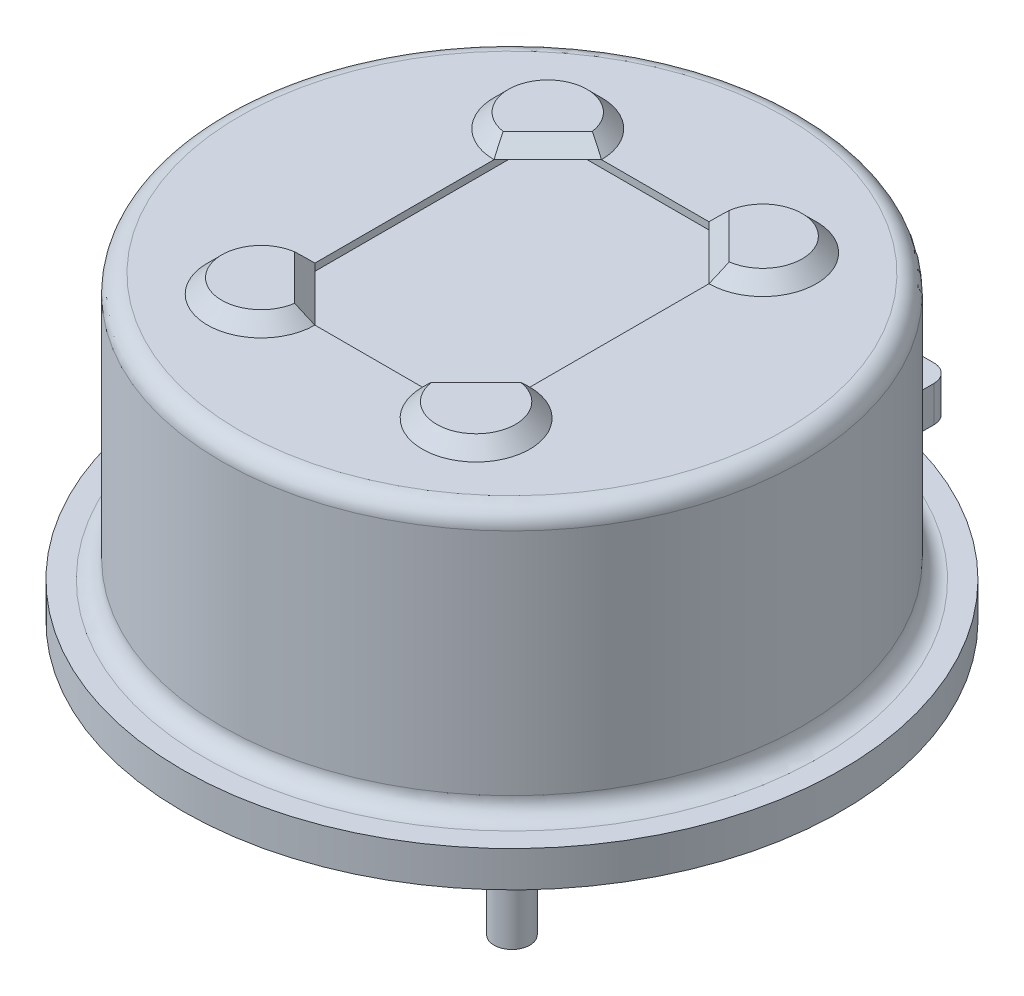
SolidWorks part; units mm, degrees
ref_plane "Front Plane" through (0, 0, 0) normal (0, 0, 1) x (1, 0, 0)
ref_plane "Top Plane" through (0, 0, 0) normal (0, 1, 0) x (1, 0, 0)
ref_plane "Right Plane" through (0, 0, 0) normal (1, 0, 0) x (0, 0, -1)
sketch "Sketch1" plane through (0, 0, 0) normal (0, 1, 0) x (1, 0, 0)
  circle A0 centre (0, 0) radius 4.05
  dimension "D1" = 8.1
extrude "Base Extrusion" add sketch "Sketch1" along normal blind 4.2
sketch "Sketch2" plane through (0, 4.2, 0) normal (0, 1, 0) x (1, 0, 0)
  line L1 (1.5, -2) -> (-1.5, -2)
  line L2 (1.5, -2) -> (1.5, 2)
  line L3 (1.5, 2) -> (-1.5, 2)
  line L4 (-1.5, -2) -> (-1.5, 2)
  line L5 (1.5, -2) -> (-1.5, 2) construction
  line L6 (1.5, 2) -> (-1.5, -2) construction
  point P0 (0, 0)
  dimension "D1" = 3
  dimension "D2" = 4
extrude "Window" cut sketch "Sketch2" against normal blind 0.1
sketch "Sketch6" plane through (0, 4.2, 0) normal (0, 1, 0) x (1, 0, 0)
  line L0 (-0.75, 2) -> (-1.5, 1.25)
  line L1 (0.75, 2) -> (1.5, 1.25)
  line L2 (1.5, -1.25) -> (0.75, -2)
  line L3 (-1.5, -1.25) -> (-0.75, -2)
  arc A0 (1.5, 1.25) -> (0.75, 2) centre (1.5, 2) ccw
  arc A1 (-0.75, 2) -> (-1.5, 1.25) centre (-1.5, 2) ccw
  arc A2 (-1.5, -1.25) -> (-0.75, -2) centre (-1.5, -2) ccw
  arc A3 (0.75, -2) -> (1.5, -1.25) centre (1.5, -2) ccw
  dimension "D1" = 1.5
extrude "Window Bumps" add sketch "Sketch6" along normal blind 0.2
chamfer "Window Bumps Chamfers" distance 0.2 angle 45 8 edges at (-2.0303, 4.4, 2.5303) (2.0303, 4.4, 2.5303) (2.0303, 4.4, -2.5303) (-2.0303, 4.4, -2.5303) (-1.125, 4.4, 1.625) (1.125, 4.4, 1.625) (1.125, 4.4, -1.625) (-1.125, 4.4, -1.625)
sketch "Sketch3" plane through (0, 0, 0) normal (0, -1, 0) x (1, 0, 0)
  circle A0 centre (0, 0) radius 4.6
  dimension "D1" = 9.2
extrude "Flange" add sketch "Sketch3" against normal blind 0.5
sketch "Sketch5" plane through (0, 0, 0) normal (0, -1, 0) x (1, 0, 0)
  line L1 (-0.575, -4.5639) -> (0.575, -4.5639)
  line L2 (-0.575, -4.5639) -> (-0.575, -5.5639)
  line L3 (-0.575, -5.5639) -> (0.575, -5.5639)
  line L4 (0.575, -4.5639) -> (0.575, -5.5639)
  circle A0 centre (0, 0) radius 4.6 construction
  dimension "D1" = 1.15
  dimension "D2" = 1
extrude "Horizontal Flange Tab" add sketch "Sketch5" against normal up to surface (0.5 mm away) up to face at (0, 0.5, -4.6)
fillet "Rounds and Fillets" radius 0.25 4 edges at (0, 4.2, 4.05) (0, 0.5, -4.05) (-0.575, 0.25, -5.5639) (0.575, 0.25, -5.5639)
sketch "Sketch4" plane through (0, 0, 0) normal (0, -1, 0) x (1, 0, 0)
  line L0 (-1.7961, -1.7961) -> (1.7961, 1.7961) construction
  line L1 (0, 0) -> (-1.7961, 1.7961) construction
  circle A0 centre (0, 0) radius 2.54 construction
  circle A1 centre (-1.7961, -1.7961) radius 0.25
  circle A2 centre (1.7961, 1.7961) radius 0.25
  circle A3 centre (-1.7961, 1.7961) radius 0.25
  dimension "D1" = 5.08
  dimension "D2" = 0.5
extrude "Leads" add sketch "Sketch4" along normal blind 13.2
ref_plane "Sensor Plane" through (0, 3.45, 0) normal (0, 1, 0) x (1, 0, 0)
sketch "Sketch7" plane through (0, 3.45, 0) normal (0, 1, 0) x (1, 0, 0)
  line L1 (-1, -1.5) -> (1, -1.5)
  line L2 (-1, -1.5) -> (-1, 1.5)
  line L3 (-1, 1.5) -> (1, 1.5)
  line L4 (1, -1.5) -> (1, 1.5)
  line L5 (-1, -1.5) -> (1, 1.5) construction
  line L6 (-1, 1.5) -> (1, -1.5) construction
  point P0 (0, 0)
  dimension "D1" = 2
  dimension "D2" = 3
extrude "Field of View Projection" [suppressed] add sketch "Sketch7" along normal blind 30 separate body
draft "Horizontal Field of View" [suppressed] type of draft neutral plane draft angle 35.5 faces to draft 2 parameters "D1"=35.5
draft "Vertical Field of View" [suppressed] type of draft neutral plane draft angle 35.5 faces to draft 2 parameters "D1"=35.5
ref_plane "Leads Trim Plane" through (0, -2, 0) normal (0, 1, 0) x (1, 0, 0)
other "Leads Trim"
